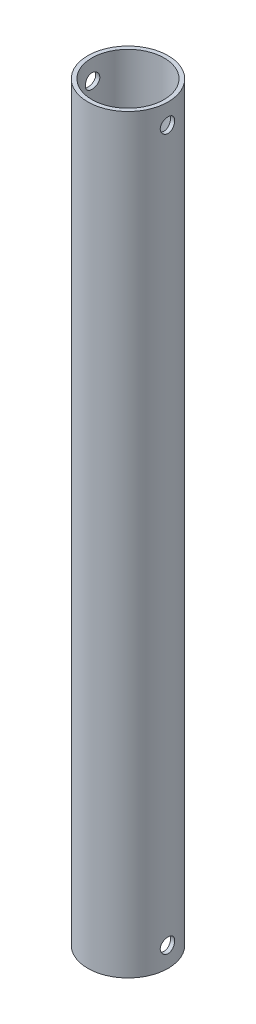
SolidWorks part; units mm, degrees
other "Boss-Extrude"
material "Toray T700"
ref_plane "Front" through (0, 0, 0) normal (0, 0, 1) x (1, 0, 0)
ref_plane "Top" through (0, 0, 0) normal (0, 1, 0) x (1, 0, 0)
ref_plane "Right" through (0, 0, 0) normal (1, 0, 0) x (0, 0, -1)
sketch "Sketch1" plane through (0, 0, 0) normal (0, 1, 0) x (1, 0, 0)
  line L5 (4.7969, 0) -> (-5.97, 0) construction
  circle A0 centre (0, 0) radius 10
  circle A1 centre (0, 0) radius 9
  dimension "D1" = 20
  dimension "D2" = 18
extrude "Boss-Extrude1" add sketch "Sketch1" along normal blind 187
ref_axis "Axis1" through (0, 0, 50) along (0, 0, -1)
ref_axis "Axis3" through (0, 187, 0) along (0, -1, 0)
ref_plane "Plane1" through (10, 0, 0) normal (1, 0, 0) x (0, 0, -1)
ref_plane "Plane2" through (0, 93.5, 0) normal (0, 1, 0) x (1, 0, 0)
hole_wizard "M3 Clearance Hole1" positions "Sketch5" profile "Sketch6" hole size "M3" standard "DIN" end condition through all
sketch "Sketch5" plane through (10, 0, 0) normal (1, 0, 0) x (0, 0, -1)
  line L0 (-10, 0) -> (10, 0) construction
  point P0 (0, 5)
  dimension "D1" = 5
sketch "Sketch6" plane through (10, 5, 0) normal (0, 1, 0) x (0, 0, -1)
  line L0 (0, 0) -> (0, 20)
  line L1 (0, 20) -> (1.8, 20)
  line L2 (1.8, 20) -> (1.8, 0)
  line L5 (1.8, 0) -> (0, 0)
  line L11 (0, -6.35) -> (0, 107.95) construction
  dimension "Thru Hole Dia." = 3.6
  dimension "Thru Hole Depth" = 20
mirror "Mirror1" about plane through (0, 93.5, 0) normal (0, 1, 0) of "M3 Clearance Hole1"
